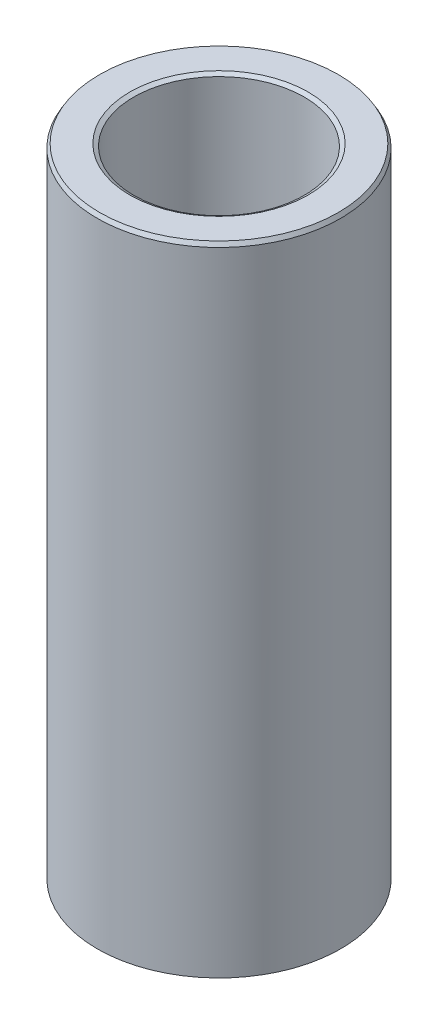
SolidWorks part; units mm, degrees
ref_plane "Front Plane" through (0, 0, 0) normal (0, 0, 1) x (1, 0, 0)
ref_plane "Top Plane" through (0, 0, 0) normal (0, 1, 0) x (1, 0, 0)
ref_plane "Right Plane" through (0, 0, 0) normal (1, 0, 0) x (0, 0, -1)
sketch "Sketch1" plane through (0, 0, 0) normal (0, 1, 0) x (1, 0, 0)
  circle A0 centre (0, 0) radius 57.5
  dimension "SLEEVE_OD" = 115
extrude "Boss-Extrude1" add sketch "Sketch1" along normal blind 301.8091
sketch "Sketch2" plane through (0, 0, 0) normal (0, 1, 0) x (1, 0, 0)
  circle A0 centre (0, 0) radius 40.2651
  dimension "BORE_D" = 80.5301
extrude "Cut-Extrude1" cut sketch "Sketch2" along normal through all
chamfer "Chamfer1" distance 1.8816 angle 30 4 edges at (0, 301.8091, 40.2651) (0, 0, 40.2651) (0, 0, 57.5) (0, 301.8091, 57.5) first distance on face at (0, 301.8091, 40.2651) first distance on face at (0, 0, 40.2651) first distance on face at (0, 301.8091, 57.5)
